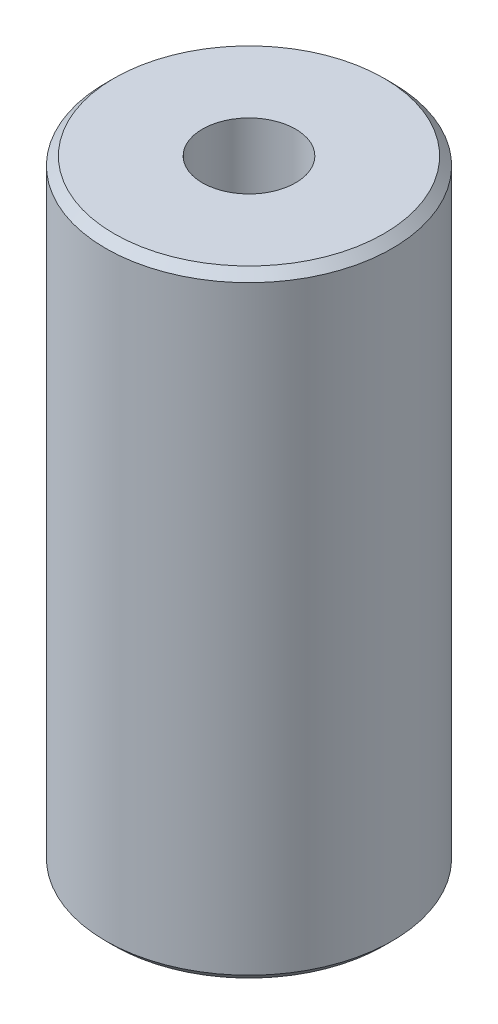
SolidWorks part; units mm, degrees
ref_plane "Front Plane" through (0, 0, 0) normal (0, 0, 1) x (1, 0, 0)
ref_plane "Top Plane" through (0, 0, 0) normal (0, 1, 0) x (1, 0, 0)
ref_plane "Right Plane" through (0, 0, 0) normal (1, 0, 0) x (0, 0, -1)
sketch "Sketch1" plane through (0, 0, 0) normal (0, 1, 0) x (1, 0, 0)
  circle A0 centre (0, 0) radius 60
  dimension "SHAFT_OD" = 120
extrude "Boss-Extrude1" add sketch "Sketch1" along normal blind 258.2589
sketch "Sketch2" plane through (0, 0, 0) normal (0, 1, 0) x (1, 0, 0)
  circle A0 centre (0, 0) radius 19.5125
  dimension "BORE_D" = 39.025
extrude "Cut-Extrude1" cut sketch "Sketch2" along normal through all
chamfer "Chamfer1" distance 3.5431 angle 45 2 edges at (0, 258.2589, 60) (0, 0, 60)
